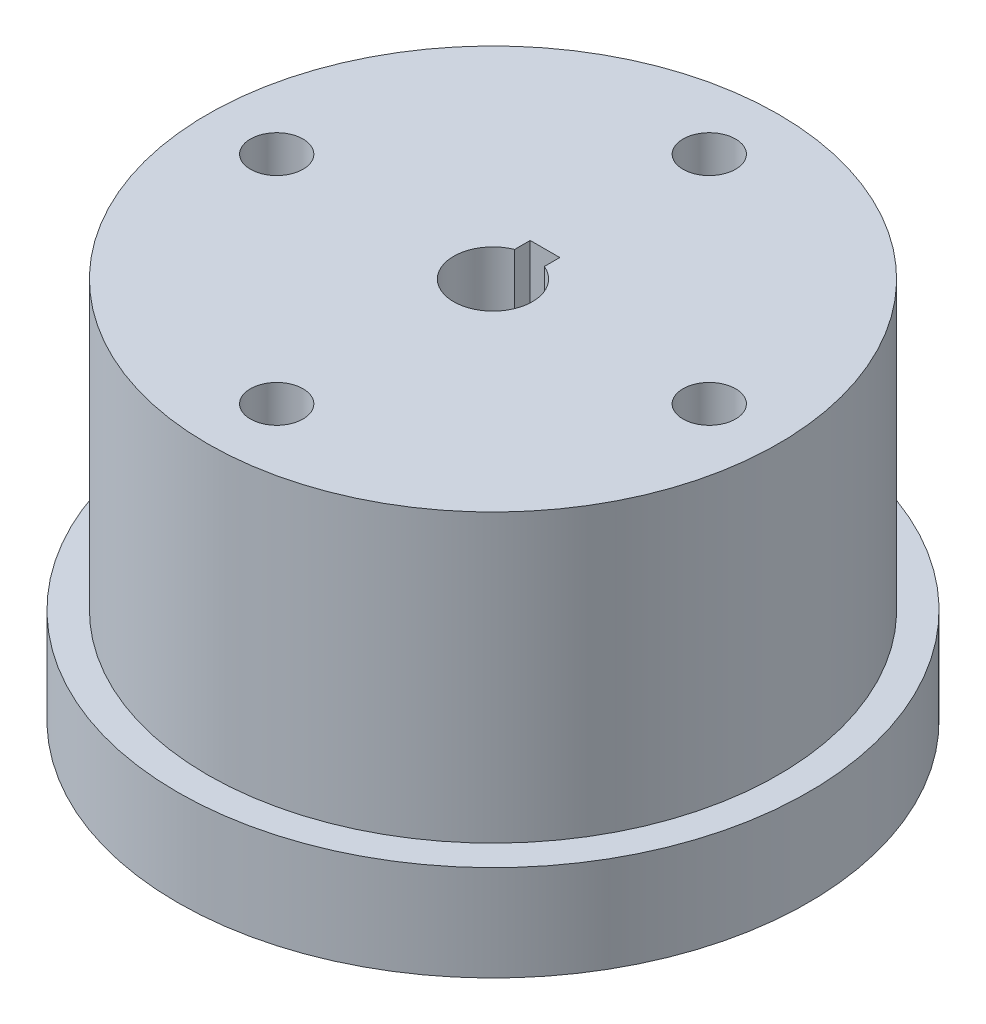
SolidWorks part; units mm, degrees
ref_plane "Front Plane" through (0, 0, 0) normal (0, 0, 1) x (1, 0, 0)
ref_plane "Top Plane" through (0, 0, 0) normal (0, 1, 0) x (1, 0, 0)
ref_plane "Right Plane" through (0, 0, 0) normal (1, 0, 0) x (0, 0, -1)
sketch "Sketch1" plane through (0, 0, 0) normal (0, 1, 0) x (1, 0, 0)
  circle A0 centre (0, 0) radius 33
extrude "Boss-Extrude1" add sketch "Sketch1" along normal blind 10
sketch "Sketch2" plane through (0, 10, 0) normal (0, 1, 0) x (1, 0, 0)
  circle A0 centre (0, 0) radius 29.86
extrude "Boss-Extrude2" add sketch "Sketch2" along normal blind 30
sketch "Sketch3" plane through (0, 40, 0) normal (0, 1, 0) x (1, 0, 0)
  line L1 (0, 22.6274) -> (-22.6274, 0)
  line L2 (-22.6274, 0) -> (0, -22.6274)
  line L3 (0, -22.6274) -> (22.6274, 0)
  line L4 (22.6274, 0) -> (0, 22.6274)
  circle A0 centre (0, 0) radius 16 construction
  circle A1 centre (0, 22.6274) radius 2.75
  circle A2 centre (22.6274, 0) radius 2.75
  circle A3 centre (0, -22.6274) radius 2.75
  circle A4 centre (-22.6274, 0) radius 2.75
  dimension "D1" = 32
extrude "Cut-Extrude1" cut sketch "Sketch3" against normal blind 54 contours L4 A1 L1 | L1 A1 L4 | L3 A2 L4 | L4 A2 L3 | L2 A3 L3 | L3 A3 L2 | L1 A4 L2 | L2 A4 L1 region at (0, 40, -20.9768) region at (0, 40, -23.1776) region at (-20.9768, 40, 0) region at (-23.1776, 40, 0) region at (23.1776, 40, 0) region at (20.9768, 40, 0) region at (0, 40, 20.9768) region at (0, 40, 23.1776)
sketch "Sketch4" plane through (0, 40, 0) normal (0, 1, 0) x (1, 0, 0)
  line L0 (0, 4.12) -> (0, 5.44)
  line L1 (0, 5.44) -> (1.55, 5.44)
  line L2 (0, 5.44) -> (-1.55, 5.44)
  line L3 (-1.55, 5.44) -> (-1.55, 3.8173)
  line L4 (1.55, 5.44) -> (1.55, 3.8173)
  circle A0 centre (0, 0) radius 4.12
extrude "Cut-Extrude2" cut sketch "Sketch4" against normal blind 54 contours A0 | A0 L4 L1 L0 | A0 L0 L2 L3 region at (-0.8023, 40, -4.7275) region at (0.8023, 40, -4.7275) region at (0, 40, 0)
